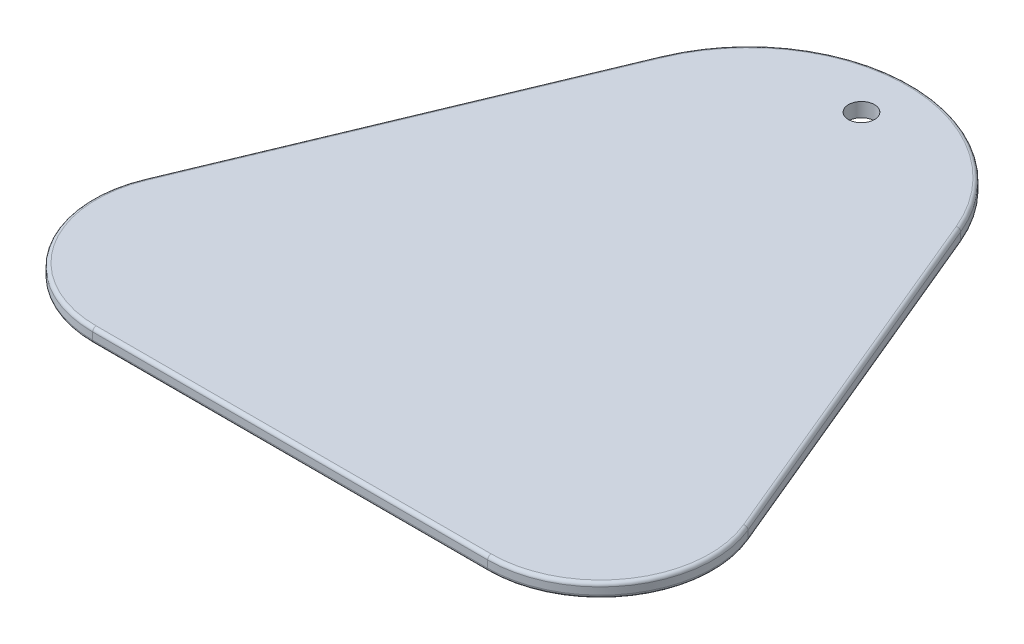
SolidWorks part; units mm, degrees
material "Pine"
ref_plane "Front Plane" through (0, 0, 0) normal (0, 0, 1) x (1, 0, 0)
ref_plane "Top Plane" through (0, 0, 0) normal (0, 1, 0) x (1, 0, 0)
ref_plane "Right Plane" through (0, 0, 0) normal (1, 0, 0) x (0, 0, -1)
sketch "Sketch1" plane through (0, 0, 0) normal (0, 1, 0) x (1, 0, 0)
  line L0 (0, 457.2) -> (0, 0) construction
  line L1 (-177.8, 0) -> (0, 0) construction
  line L2 (177.8, 0) -> (0, 0) construction
  line L3 (134.8154, 367.3231) -> (271.5846, 39.0769)
  line L4 (-134.8154, 367.3231) -> (-271.5846, 39.0769)
  line L5 (-177.8, -101.6) -> (177.8, -101.6)
  arc A0 (134.8154, 367.3231) -> (-134.8154, 367.3231) centre (0, 311.15) ccw
  arc A1 (-271.5846, 39.0769) -> (-177.8, -101.6) centre (-177.8, 0) ccw
  arc A2 (177.8, -101.6) -> (271.5846, 39.0769) centre (177.8, 0) ccw
  circle A3 centre (0, 412.75) radius 11.7094
  dimension "D1" = 355.6
  dimension "D2" = 146.05
  dimension "D4" = 101.6
  dimension "D5" = 44.45
  dimension "D6" = 23.4188
  dimension "D3" = 558.8
extrude "Boss-Extrude1" add sketch "Sketch1" along normal blind 12.7
fillet "Fillet2" radius 3.175 6 edges at (-262.3363, 12.7, 56.3575) (-203.2, 12.7, -203.2) (0, 12.7, -457.2) (203.2, 12.7, -203.2) (262.3363, 12.7, 56.3575) (0, 12.7, 101.6)
fillet "Fillet3" radius 3.175 6 edges at (-262.3363, 0, 56.3575) (-203.2, 0, -203.2) (0, 0, -457.2) (203.2, 0, -203.2) (262.3363, 0, 56.3575) (0, 0, 101.6)
sketch "Sketch2" plane through (0, 0, 0) normal (0, -1, 0) x (1, 0, 0)
  circle A0 centre (0, -412.75) radius 11.7094 construction
  circle A1 centre (198.2879, 44.9469) radius 2.25 construction
  spline S0 degree 3 poles (-258.1398, 46.5911) (-258.4401, 46.5907) (-258.5923, 46.5759) (-258.9013, 46.5121) (-259.0594, 46.4622) (-259.3641, 46.3263) (-259.5149, 46.2381) (-259.7913, 46.0289) (-259.9184, 45.9073) (-260.1415, 45.6367) (-260.2342, 45.4924) (-260.3846, 45.1876) (-260.4394, 45.0336) (-260.5523, 44.5677) (-260.556, 44.2658) (-260.4628, 43.7059) (-260.3679, 43.4531) (-260.1012, 42.9952) (-259.9342, 42.7984) (-259.5377, 42.4646) (-259.3132, 42.3325) (-258.8163, 42.1471) (-258.5398, 42.0936) (-258.1032, 42.0972) (-257.9513, 42.1126) (-257.6472, 42.1766) (-257.494, 42.225) (-257.1885, 42.3615) (-257.0418, 42.4471) (-256.7624, 42.6583) (-256.6358, 42.7797) (-256.4136, 43.0491) (-256.3198, 43.1954) (-256.1714, 43.4956) (-256.1165, 43.6498) (-256.0421, 43.9524) (-256.0218, 44.1045) (-256.0111, 44.3971) (-256.0201, 44.5383) (-256.0625, 44.8122) (-256.0964, 44.9456) (-256.1842, 45.1972) (-256.2383, 45.3163) (-256.4282, 45.6553) (-256.5938, 45.8587) (-256.8845, 46.1128) (-256.9889, 46.1896) (-257.2132, 46.3263) (-257.3341, 46.3864) (-257.5861, 46.4845) (-257.7179, 46.5231) (-257.9943, 46.5763) (-258.1398, 46.5911) (-258.4401, 46.5907) (-258.5923, 46.5759) knots -0.03125 -0.03125 0 0 0.03125 0.03125 0.0625 0.0625 0.09375 0.09375 0.125 0.125 0.15625 0.15625 0.1875 0.1875 0.25 0.25 0.3125 0.3125 0.375 0.375 0.4375 0.4375 0.5 0.5 0.53125 0.53125 0.5625 0.5625 0.59375 0.59375 0.625 0.625 0.65625 0.65625 0.6875 0.6875 0.71875 0.71875 0.75 0.75 0.78125 0.78125 0.8125 0.8125 0.875 0.875 0.90625 0.90625 0.9375 0.9375 0.96875 0.96875 1 1 1.03125 1.03125 1.0625 only from (-258.29, 46.5909) to (-258.29, 46.5909) construction
  spline S1 degree 3 poles (-198.0125, -13.5042) (-198.302, -13.5039) (-198.4492, -13.5177) (-198.7495, -13.5782) (-198.9042, -13.6259) (-199.205, -13.7578) (-199.3554, -13.8441) (-199.6332, -14.0509) (-199.7622, -14.1721) (-199.9889, -14.4423) (-200.084, -14.5876) (-200.2376, -14.8902) (-200.2943, -15.0434) (-200.3741, -15.3512) (-200.396, -15.5009) (-200.4115, -15.7939) (-200.4047, -15.9383) (-200.348, -16.3508) (-200.2632, -16.6026) (-200.0184, -17.0605) (-199.8618, -17.2606) (-199.4822, -17.6051) (-199.2645, -17.7441) (-198.7753, -17.9442) (-198.4993, -18.0056) (-198.0604, -18.0109) (-197.9072, -17.998) (-197.6006, -17.9382) (-197.4458, -17.8915) (-197.1377, -17.7577) (-196.9897, -17.6732) (-196.7077, -17.4643) (-196.5788, -17.3432) (-196.3525, -17.0743) (-196.2556, -16.9268) (-196.1016, -16.6236) (-196.0434, -16.4659) (-195.9637, -16.1552) (-195.9415, -15.9991) (-195.928, -15.6996) (-195.9362, -15.5546) (-195.978, -15.2731) (-196.0118, -15.1376) (-196.0996, -14.8828) (-196.1538, -14.7623) (-196.2811, -14.5339) (-196.3546, -14.4256) (-196.5164, -14.2265) (-196.6048, -14.135) (-196.892, -13.8844) (-197.1148, -13.7484) (-197.4786, -13.6072) (-197.6054, -13.5702) (-197.8717, -13.5187) (-198.0125, -13.5042) (-198.302, -13.5039) (-198.4492, -13.5177) knots -0.03125 -0.03125 0 0 0.03125 0.03125 0.0625 0.0625 0.09375 0.09375 0.125 0.125 0.15625 0.15625 0.1875 0.1875 0.21875 0.21875 0.25 0.25 0.3125 0.3125 0.375 0.375 0.4375 0.4375 0.5 0.5 0.53125 0.53125 0.5625 0.5625 0.59375 0.59375 0.625 0.625 0.65625 0.65625 0.6875 0.6875 0.71875 0.71875 0.75 0.75 0.78125 0.78125 0.8125 0.8125 0.84375 0.84375 0.875 0.875 0.9375 0.9375 0.96875 0.96875 1 1 1.03125 1.03125 1.0625 only from (-198.1572, -13.5041) to (-198.1572, -13.5041) construction
  line B0 (-35.1831, -448.0896) -> (35.2623, -377.2919) construction
  line B1 (-35.0813, -377.3268) -> (35.0349, -448.1874) construction
  arc B2 (-24.8967, -369.0543) -> (24.9629, -369.1237) centre (0.0553, -353.1844) ccw
  arc B3 (-43.3115, -387.7683) -> (-24.8967, -369.0543) centre (7.5218, -419.3717) cw
  arc B4 (24.9629, -369.1237) -> (43.3314, -387.889) centre (-2.6738, -414.5489) cw
  arc B5 (43.3314, -387.889) -> (43.2268, -437.8072) centre (60.0346, -412.8832) ccw
  arc B6 (43.2268, -437.8072) -> (24.8418, -456.1117) centre (-3.0633, -409.6986) cw
  arc B7 (-25.0764, -456.007) -> (-43.3459, -437.6866) centre (3.0677, -409.6717) cw
  arc B8 (-43.3115, -387.7683) -> (-43.3459, -437.6866) centre (-60.0893, -412.7159) cw
  arc B9 (-25.0764, -456.007) -> (24.8418, -456.1117) centre (-0.1514, -472.3272) cw
  circle B10 centre (-30.0349, -382.6616) radius 2.25
  circle B11 centre (30.0691, -382.7454) radius 2.25
  circle B12 centre (29.9852, -442.8494) radius 2.25
  circle B13 centre (-30.1193, -442.7659) radius 2.25
  circle B14 centre (0, -412.75) radius 12.27
  line B15 (-263.3188, 49.6643) -> (-193.099, -21.0937) construction
  arc B16 (-184.8907, 39.2168) -> (-184.9224, -10.7015) centre (-168.1511, 14.2471) ccw
  arc B17 (-271.5337, 39.2108) -> (-271.4952, -10.7075) centre (-288.275, 14.2387) cw
  arc B18 (-253.1989, -29.0012) -> (-203.2806, -29.0329) centre (-228.25, -45.285) cw
  circle B19 centre (-258.2646, 44.3368) radius 2.25
  line B20 (193.1754, -20.4839) -> (263.5822, 50.3523) construction
  line B21 (193.2385, 50.279) -> (263.3935, -20.5433) construction
  arc B22 (271.657, 39.7597) -> (271.5797, -10.1586) centre (288.3738, 14.7746) ccw
  arc B23 (185.0141, 39.833) -> (185.0069, -10.0853) centre (168.2499, 14.8763) cw
  arc B24 (203.2864, -28.3958) -> (253.2046, -28.4731) centre (228.2203, -44.7023) cw
  circle B25 centre (228.3392, 14.875) radius 12.27
sketch_block_instance "Block1-1"
sketch_block "Block1"
sketch_block_instance "Block1-4"
sketch_block_instance "Block1-5"
sketch "Sketch3" plane through (0, 0, 0) normal (0, -1, 0) x (-1, 0, 0)
  line L0 (0, -101.6) -> (0.1514, 472.3272) construction
  line L1 (177.8, -101.6) -> (-177.8, -101.6) construction
